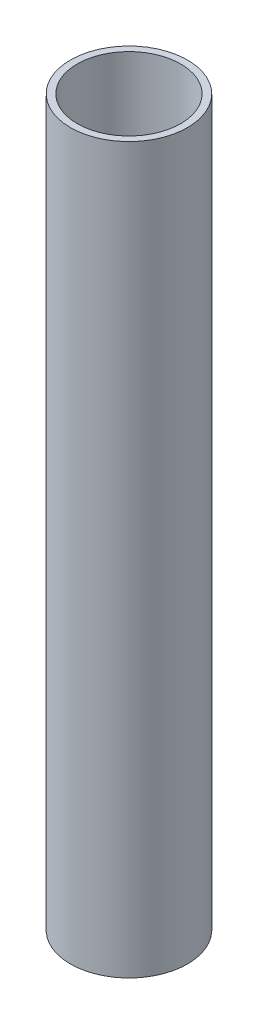
SolidWorks part; units mm, degrees
material "Corrugated Paper"
ref_plane "Front Plane" through (0, 0, 0) normal (0, 0, 1) x (1, 0, 0)
ref_plane "Top Plane" through (0, 0, 0) normal (0, 1, 0) x (1, 0, 0)
ref_plane "Right Plane" through (0, 0, 0) normal (1, 0, 0) x (0, 0, -1)
sketch "Sketch2" plane through (0, 0, 0) normal (0, 1, 0) x (1, 0, 0)
  circle A0 centre (0, 0) radius 43
  circle A1 centre (0, 0) radius 38
  dimension "D1" = 86
  dimension "D2" = 76
extrude "body" add sketch "Sketch2" along normal blind 532
equation "\"paper_size\" = 600mm"
equation "\"cb_roll_d_outer\" = 86mm"
equation "\"cb_roll_d_inner\" = 76mm"
equation "\"D1@body\"=\"paper_size\" - \"attached_len\" - 10"
equation "\"attached_len\" = \"spring_l_max\" * 2 - \"spring_l_min\" + 18"
equation "\"helper_d\" = 92mm"
equation "\"outer_d\" = 112mm"
equation "\"spring_l_max\" = 25mm"
equation "\"spring_l_min\" = 10mm"
equation "\"D1@Sketch2\"=\"cb_roll_d_outer\""
equation "\"D2@Sketch2\"=\"cb_roll_d_inner\""
